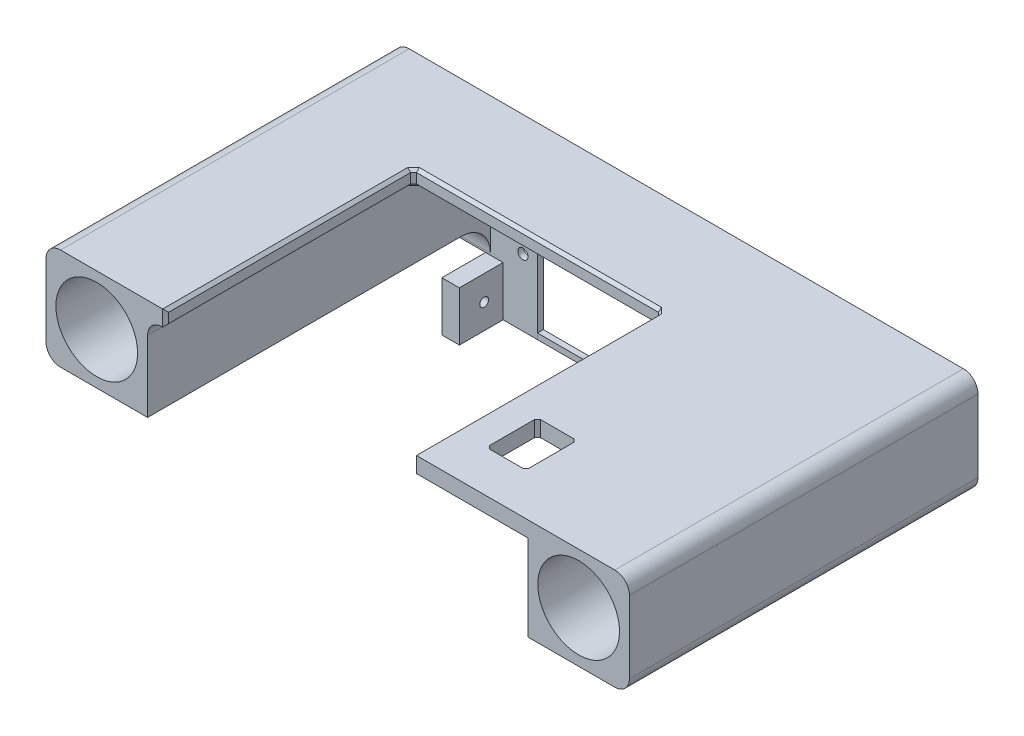
SolidWorks part; units mm, degrees
ref_plane "Front Plane" through (0, 0, 0) normal (0, 0, 1) x (1, 0, 0)
ref_plane "Top Plane" through (0, 0, 0) normal (0, 1, 0) x (1, 0, 0)
ref_plane "Right Plane" through (0, 0, 0) normal (1, 0, 0) x (0, 0, -1)
sketch "Sketch1" plane through (0, 0, 0) normal (0, 0, 1) x (1, 0, 0)
  line L1 (-50, 17.4) -> (-15.2, 17.4)
  line L2 (-50, 17.4) -> (-50, -17.4)
  line L5 (50, 12.0226) -> (-15.1728, 12.0226)
  line L6 (-50, -17.4) -> (-15.2, 17.4) construction
  line L7 (-15.2, 17.4) -> (50, 17.4)
  line L9 (50, 17.4) -> (50, 12.0226)
  line L16 (-15.1728, 12.0226) -> (-15.1728, -17.4)
  line L17 (-15.1728, -17.4) -> (-50, -17.4)
  circle A0 centre (-32.6, 0) radius 14
  point P6 (-32.6, 17.4)
  dimension "D1" = 28
  dimension "D3" = 34.8
  dimension "D5" = 100
extrude "Boss-Extrude1" add sketch "Sketch1" along normal blind 119.5
mirror "Mirror1" about plane through (50, 17.4, 119.5) normal (-1, 0, 0) of "Boss-Extrude1"
sketch "Sketch5" plane through (0, 17.4, 0) normal (0, 1, 0) x (1, 0, 0)
  line L0 (150, -119.5) -> (-50, -119.5) construction
  line L1 (-9, -119.5) -> (76, -119.5)
  line L2 (-9, -119.5) -> (-9, -34.5)
  line L3 (-9, -34.5) -> (76, -34.5)
  line L4 (76, -119.5) -> (76, -34.5)
  line L5 (-50, -119.5) -> (-50, 0) construction
  dimension "D1" = 41
  dimension "D2" = 85
  dimension "D3" = 85
extrude "Cut-Extrude2" cut sketch "Sketch5" against normal blind 10
chamfer "Chamfer2" distance 1 angle 45 10 edges at (76, 12.0226, 77) (76, 14.7113, 34.5) (76, 17.4, 77) (76, 14.7113, 119.5) (33.5, 12.0226, 34.5) (33.5, 17.4, 34.5) (-9, 12.0226, 77) (-9, 14.7113, 119.5) (-9, 17.4, 77) (-9, 14.7113, 34.5)
sketch "Sketch6" plane through (0, 0, 0) normal (0, 0, -1) x (-1, 0, 0)
  line L1 (50, 17.4) -> (50, -17.4) construction
  line L3 (9, 0) -> (9, 17.4) construction
  line L4 (-150, 17.4) -> (50, 17.4) construction
  line L5 (15.1728, 12.0226) -> (-115.1728, 12.0226) construction
  line L6 (-74.5, 12.0226) -> (-59.5, 12.0226)
  line L7 (-74.5, 12.0226) -> (-74.5, -44.9774)
  line L8 (-74.5, -44.9774) -> (-59.5, -44.9774)
  line L9 (-59.5, 12.0226) -> (-59.5, -44.9774)
  line L10 (-67, 12.0226) -> (-67, -44.9774) construction
  line L11 (50, -27.9774) -> (-1, -27.9774)
  line L17 (50, -27.9774) -> (50, -15.9774)
  line L18 (50, -15.9774) -> (-1, -15.9774)
  line L19 (-1, -27.9774) -> (-1, -15.9774)
  dimension "D1" = 41
  dimension "D2" = 76
  dimension "D3" = 15
  dimension "D4" = 28
  dimension "D5" = 12
  dimension "D6" = 10
  dimension "D7" = 57
extrude "Boss-Extrude3" add sketch "Sketch6" against normal blind 2
sketch "Sketch7" plane through (0, 0, 0) normal (0, 0, -1) x (-1, 0, 0)
  line L0 (4, 12.0226) -> (4, -15.9774) construction
  line L1 (15.1728, 12.0226) -> (-59.5, 12.0226) construction
  line L2 (15.1728, -15.9774) -> (-1, -15.9774) construction
  line L3 (50, 17.4) -> (50, -27.9774) construction
  line L4 (4, -15.9774) -> (4, -27.9774) construction
  line L5 (-1, -27.9774) -> (50, -27.9774) construction
  line L6 (-67, 7.0226) -> (-67, -44.9774) construction
  line L7 (-67, 12.0226) -> (-67, 7.0226) construction
  line L8 (-59.5, 7.0226) -> (-74.5, 7.0226) construction
  line L9 (-59.5, -44.9774) -> (-59.5, 12.0226) construction
  line L10 (-74.5, 12.0226) -> (-74.5, -44.9774) construction
  line L11 (-74.5, -44.9774) -> (-59.5, -44.9774) construction
  circle A0 centre (4, -21.9774) radius 1.75
  circle A1 centre (-67, 7.0226) radius 1.75
  circle A2 centre (-67, -39.9774) radius 1.75
  dimension "D1" = 3.5
  dimension "D3" = 3.5
  dimension "D5" = 3.5
  dimension "D2" = 46
  dimension "D4" = 5
  dimension "D6" = 52
extrude "Cut-Extrude3" cut sketch "Sketch7" against normal blind 2
fillet "Fillet1" radius 10 1 edges at (-32.5864, -17.4, 2)
fillet "Fillet2" radius 10 1 edges at (59.5, 12.0226, 1)
sketch "Sketch8" plane through (0, 17.4, 0) normal (0, 1, 0) x (1, 0, 0)
  line L1 (86.5656, -87.568) -> (100.0656, -87.568)
  line L2 (86.5656, -87.568) -> (86.5656, -105.068)
  line L3 (86.5656, -105.068) -> (100.0656, -105.068)
  line L4 (100.0656, -87.568) -> (100.0656, -105.068)
  dimension "D1" = 13.5
  dimension "D2" = 17.5
extrude "Cut-Extrude4" cut sketch "Sketch8" against normal blind 10
chamfer "Chamfer4" distance 1 angle 45 4 edges at (100.0656, 14.7113, 87.568) (86.5656, 14.7113, 87.568) (86.5656, 14.7113, 105.068) (100.0656, 14.7113, 105.068)
sketch "Sketch10" plane through (0, 0, 0) normal (0, 0, -1) x (-1, 0, 0)
  line L1 (7.7279, -17.1704) -> (16.8688, -17.1704)
  line L2 (7.7279, -17.1704) -> (7.7279, 13.0982)
  line L3 (7.7279, 13.0982) -> (16.8688, 13.0982)
  line L4 (16.8688, -17.1704) -> (16.8688, 13.0982)
extrude "Boss-Extrude4" add sketch "Sketch10" against normal blind 2
fillet "Fillet3" radius 5 1 edges at (-7.7279, -15.9774, 1)
fillet "Fillet4" radius 5 1 edges at (-7.7279, 12.0226, 1)
fillet "Fillet5" radius 5 7 edges at (150, 17.4, 59.75) (150, -17.4, 59.75) (-50, -27.6887, 2) (-50, -20.3289, 4.9289) (-50, 17.4, 59.75) (-15.1728, 12.0226, 60.75) (-50, -17.4, 65.75)
sketch "Sketch11" plane through (0, 0, 0) normal (0, 0, -1) x (-1, 0, 0)
  line L1 (-74.5, 12.0226) -> (-115.1728, 12.0226)
  line L2 (-74.5, 12.0226) -> (-74.5, -44.9774)
  line L3 (-74.5, -44.9774) -> (-115.1728, -44.9774)
  line L4 (-115.1728, 12.0226) -> (-115.1728, -44.9774)
extrude "Boss-Extrude5" add sketch "Sketch11" against normal blind 2
sketch "Sketch13" plane through (0, -44.9774, 0) normal (0, -1, 0) x (-1, 0, 0)
  line L1 (-115.1728, -2) -> (-79.6728, -2)
  line L2 (-115.1728, -2) -> (-115.1728, -17)
  line L3 (-115.1728, -17) -> (-79.6728, -17)
  line L4 (-79.6728, -2) -> (-79.6728, -17)
  dimension "D1" = 15
  dimension "D2" = 35.5
extrude "Boss-Extrude6" add sketch "Sketch13" against normal blind 6
sketch "Sketch14" plane through (0, 0, 0) normal (0, 0, -1) x (-1, 0, 0)
  line L0 (-115.1728, -44.9774) -> (-59.5, -44.9774) construction
  line L1 (-115.1728, -17.4) -> (-113.1728, -17.4)
  line L2 (-115.1728, -17.4) -> (-115.1728, -44.9774)
  line L3 (-115.1728, -44.9774) -> (-113.1728, -44.9774)
  line L4 (-113.1728, -17.4) -> (-113.1728, -44.9774)
  dimension "D1" = 2
extrude "Cut-Extrude5" cut sketch "Sketch14" against normal blind 17
sketch "Sketch15" plane through (0, 0, 0) normal (0, 0, -1) x (-1, 0, 0)
  line L0 (-113.1728, -44.9774) -> (-59.5, -44.9774) construction
  line L1 (-1, -27.9774) -> (16.8, -27.9774)
  line L2 (-1, -27.9774) -> (-1, -44.9774)
  line L3 (-1, -44.9774) -> (16.8, -44.9774)
  line L4 (16.8, -27.9774) -> (16.8, -44.9774)
  dimension "D1" = 17.8
extrude "Boss-Extrude7" add sketch "Sketch15" against normal blind 2
sketch "Sketch16" plane through (-16.8, 0, 0) normal (-1, 0, 0) x (0, 0, 1)
  line L1 (2, -44.9774) -> (17, -44.9774)
  line L2 (2, -44.9774) -> (2, -27.9774)
  line L3 (2, -27.9774) -> (17, -27.9774)
  line L4 (17, -44.9774) -> (17, -27.9774)
  dimension "D1" = 15
extrude "Boss-Extrude8" add sketch "Sketch16" against normal blind 6
fillet "Fillet6" radius 2 1 edges at (1, -15.9774, 1)
sketch "Sketch17" plane through (0, 0, 0) normal (0, 0, -1) x (-1, 0, 0)
  line L0 (-59.5, -44.9774) -> (-59.5, 2.0226) construction
  line L1 (-1, -44.9774) -> (-59.5, -44.9774)
  line L2 (-1, -44.9774) -> (-1, -42.9774)
  line L3 (-1, -42.9774) -> (-59.5, -42.9774)
  line L4 (-59.5, -44.9774) -> (-59.5, -42.9774)
  dimension "D1" = 2
extrude "Boss-Extrude9" add sketch "Sketch17" against normal blind 2 separate body
sketch "Sketch18" plane through (113.1728, 0, 0) normal (1, 0, 0) x (0, 0, -1)
  line L1 (-2, -38.9774) -> (-17, -38.9774)
  line L2 (-2, -38.9774) -> (-2, -19.5089)
  line L3 (-2, -19.5089) -> (-17, -19.5089)
  line L4 (-17, -38.9774) -> (-17, -19.5089)
  point P5 (0, 0)
extrude "Boss-Extrude10" add sketch "Sketch18" against normal blind 6
sketch "Sketch19" plane through (113.1728, 0, 0) normal (1, 0, 0) x (0, 0, -1)
  line L0 (-8.5, -44.9774) -> (-8.5, -19.5089) construction
  line L2 (-17, -44.9774) -> (0, -44.9774) construction
  line L3 (-2, -19.5089) -> (-17, -19.5089) construction
  circle A0 centre (-8.5, -32.2432) radius 1.5
  point P6 (0, 0)
  point P7 (-8.5, -32.2432)
  dimension "D1" = 3
  dimension "D2" = 12.7342
extrude "Cut-Extrude6" cut sketch "Sketch19" against normal blind 6
sketch "Sketch21" plane through (0, -44.9774, 0) normal (0, -1, 0) x (1, 0, 0)
  line L0 (96.924, 17) -> (96.924, 0) construction
  line L1 (113.1728, 17) -> (79.6728, 17) construction
  line L2 (113.1728, 0) -> (59.5, 0) construction
  line L3 (113.1728, 17) -> (113.1728, 0) construction
  circle A0 centre (96.924, 8.5) radius 1.5
  point P4 (0, 0)
  point P5 (96.924, 8.5)
  dimension "D1" = 3
  dimension "D2" = 16.2488
  dimension "D3" = 8.5
extrude "Cut-Extrude7" cut sketch "Sketch21" against normal blind 6
sketch "Sketch22" plane through (-16.8, 0, 0) normal (-1, 0, 0) x (0, 0, 1)
  line L0 (0, -44.9774) -> (0, -27.9774) construction
  line L1 (0, -36.4774) -> (17, -36.4774) construction
  line L2 (17, -44.9774) -> (17, -27.9774) construction
  line L3 (17, -44.9774) -> (0, -44.9774) construction
  circle A0 centre (8.5, -36.4774) radius 1.5
  point P8 (0, 0)
  point P9 (0, 0)
  dimension "D1" = 3
extrude "Cut-Extrude8" cut sketch "Sketch22" against normal blind 6
